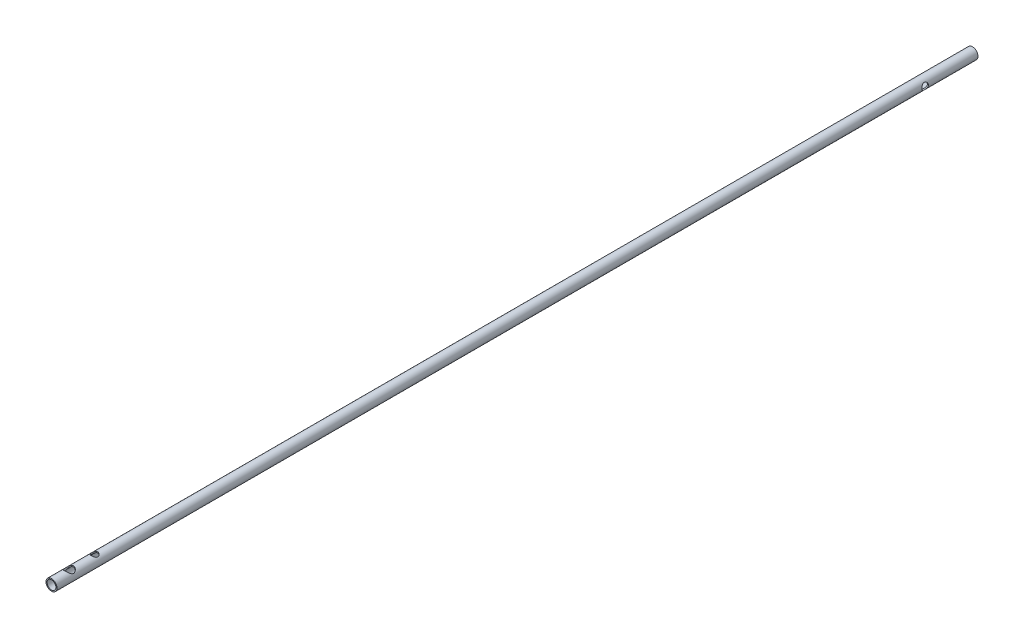
SolidWorks part; units mm, degrees
material "1060 合金"
ref_plane "正面" through (0, 0, 0) normal (0, 0, 1) x (1, 0, 0)
ref_plane "平面" through (0, 0, 0) normal (0, 1, 0) x (1, 0, 0)
ref_plane "右側面" through (0, 0, 0) normal (1, 0, 0) x (0, 0, -1)
sketch "ｽｹｯﾁ1" plane through (0, 0, 0) normal (0, 0, 1) x (1, 0, 0)
  circle A0 centre (0, 0) radius 5
  dimension "D1" = 10
extrude "押し出し-薄板1" add sketch "ｽｹｯﾁ1" along normal blind 836.5 thin thin type one direction reverse wall 1
sketch "ｽｹｯﾁ2" plane through (0, 0, 0) normal (0, 1, 0) x (1, 0, 0)
  line L0 (0, 0) -> (0, 50000) construction
  line L1 (-5, -836.5) -> (5, -836.5) construction
  circle A0 centre (0, -820.5) radius 2
  circle A1 centre (0, -797.5) radius 1.5
  circle A2 centre (0, -820.5) radius 4
  circle A3 centre (0, -797.5) radius 3
  dimension "D1" = 16
  dimension "D2" = 23
  dimension "D3" = 4
  dimension "D4" = 8
  dimension "D5" = 6
  dimension "D6" = 3
extrude "ｶｯﾄ - 押し出し1" cut sketch "ｽｹｯﾁ2" against normal through all both and the other way through all contours L0 A1 | A1 L0 | L0 A0 | A0 L0 region at (0, 0, 820.5) region at (0, 0, 797.5)
extrude "ｶｯﾄ - 押し出し2" cut sketch "ｽｹｯﾁ2<3>" along normal through all contours A2 | A3
sketch "ｽｹｯﾁ2<3>" plane through (0, 0, 0) normal (0, 1, 0) x (1, 0, 0) same geometry as "ｽｹｯﾁ2"
sketch "ｽｹｯﾁ3" plane through (0, 0, 0) normal (1, 0, 0) x (0, 0, -1)
  line L0 (0, 0) -> (50000, 0) construction
  line L1 (0, -5) -> (0, 5) construction
  circle A0 centre (-48, 0) radius 1.5
  circle A1 centre (-48, 0) radius 3
  dimension "D1" = 48
  dimension "D2" = 3
  dimension "D3" = 6
extrude "ｶｯﾄ - 押し出し3" cut sketch "ｽｹｯﾁ3" against normal through all both and the other way through all contours A0
extrude "ｶｯﾄ - 押し出し4" cut sketch "ｽｹｯﾁ3<3>" along normal blind 10 contours A1
sketch "ｽｹｯﾁ3<3>" plane through (0, 0, 0) normal (1, 0, 0) x (0, 0, -1) same geometry as "ｽｹｯﾁ3"
